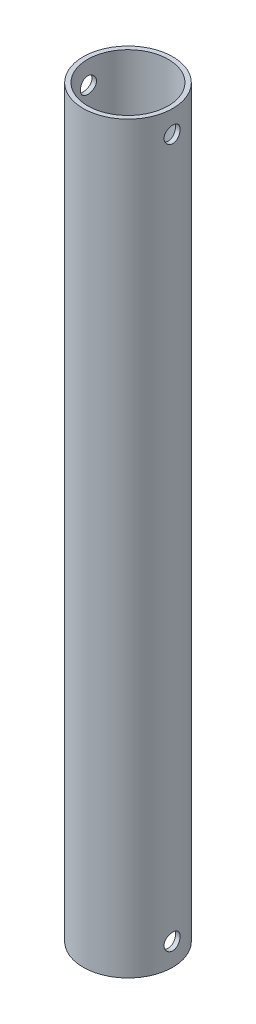
SolidWorks part; units mm, degrees
other "Boss-Extrude"
material "Toray T700"
ref_plane "Front" through (0, 0, 0) normal (0, 0, 1) x (1, 0, 0)
ref_plane "Top" through (0, 0, 0) normal (0, 1, 0) x (1, 0, 0)
ref_plane "Right" through (0, 0, 0) normal (1, 0, 0) x (0, 0, -1)
sketch "Sketch1" plane through (0, 0, 0) normal (0, 1, 0) x (1, 0, 0)
  line L5 (4.7969, 0) -> (-5.97, 0) construction
  circle A0 centre (0, 0) radius 10
  circle A1 centre (0, 0) radius 9
  dimension "D1" = 20
  dimension "D2" = 18
extrude "Boss-Extrude1" add sketch "Sketch1" along normal blind 166
ref_axis "Axis1" through (0, 0, 50) along (0, 0, -1)
ref_axis "Axis3" through (0, 166, 0) along (0, -1, 0)
ref_plane "Plane1" through (10, 0, 0) normal (1, 0, 0) x (0, 0, -1)
ref_plane "Plane2" through (0, 83, 0) normal (0, 1, 0) x (1, 0, 0)
hole_wizard "M3 Clearance Hole1" positions "Sketch5" profile "Sketch6" hole size "M3" standard "DIN" end condition through all
sketch "Sketch5" plane through (10, 0, 0) normal (1, 0, 0) x (0, 0, -1)
  line L0 (-10, 0) -> (10, 0) construction
  point P0 (0, 5)
  dimension "D1" = 5
sketch "Sketch6" plane through (10, 5, 0) normal (0, 1, 0) x (0, 0, -1)
  line L0 (0, 0) -> (0, 20)
  line L1 (0, 20) -> (1.8, 20)
  line L2 (1.8, 20) -> (1.8, 0)
  line L5 (1.8, 0) -> (0, 0)
  line L11 (0, -6.35) -> (0, 107.95) construction
  dimension "Thru Hole Dia." = 3.6
  dimension "Thru Hole Depth" = 20
mirror "Mirror1" about plane through (0, 83, 0) normal (0, 1, 0) of "M3 Clearance Hole1"
